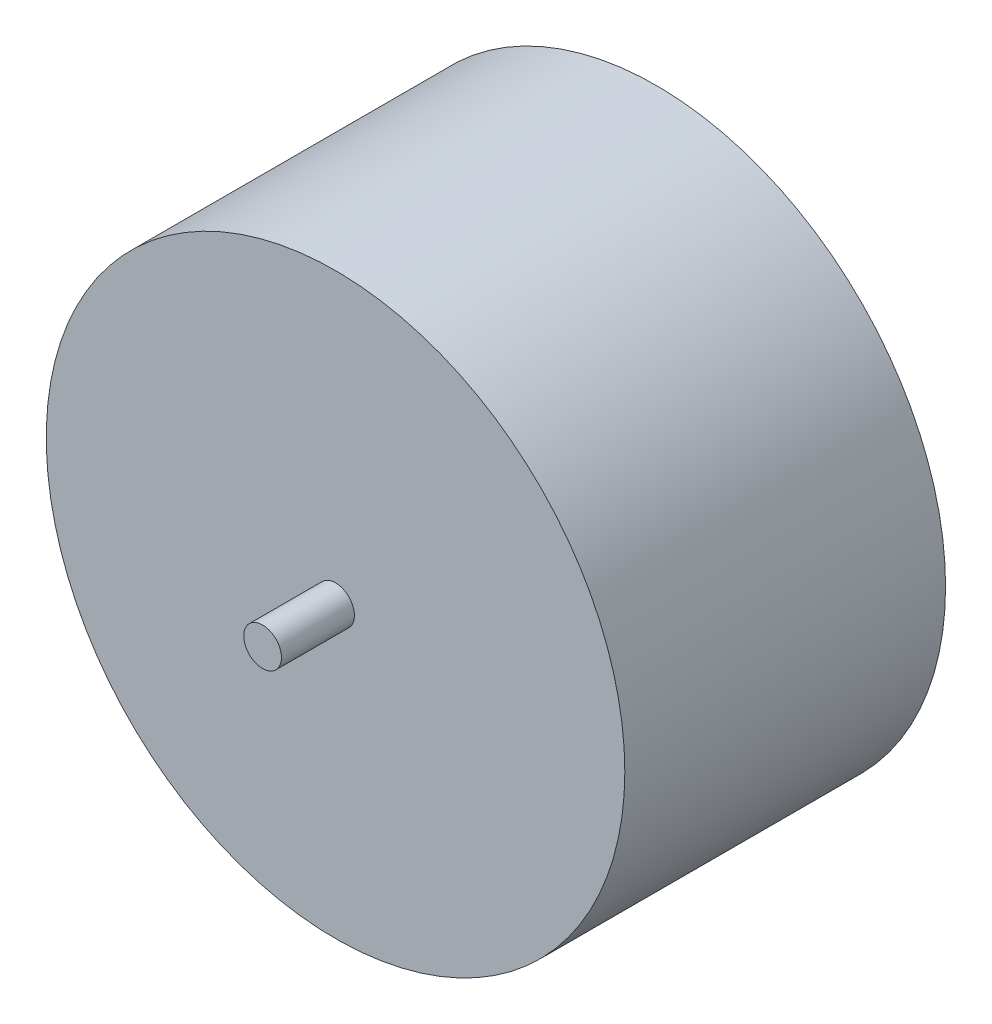
SolidWorks part; units mm, degrees
ref_plane "Plan de face" through (0, 0, 0) normal (0, 0, 1) x (1, 0, 0)
ref_plane "Plan de dessus" through (0, 0, 0) normal (0, 1, 0) x (1, 0, 0)
ref_plane "Plan de droite" through (0, 0, 0) normal (1, 0, 0) x (0, 0, -1)
sketch "Sketch1" plane through (0, 0, 0) normal (0, 0, 1) x (1, 0, 0)
  circle A0 centre (0, 0) radius 23
  dimension "D1" = 46
extrude "Boss-Extrude1" add sketch "Sketch1" along normal blind 25.5
sketch "Sketch3" plane through (0, 0, 25.5) normal (0, 0, 1) x (1, 0, 0)
  circle A0 centre (0, 0) radius 1.5
  dimension "D1" = 3
extrude "Boss-Extrude4" add sketch "Sketch3" along normal blind 5.8
